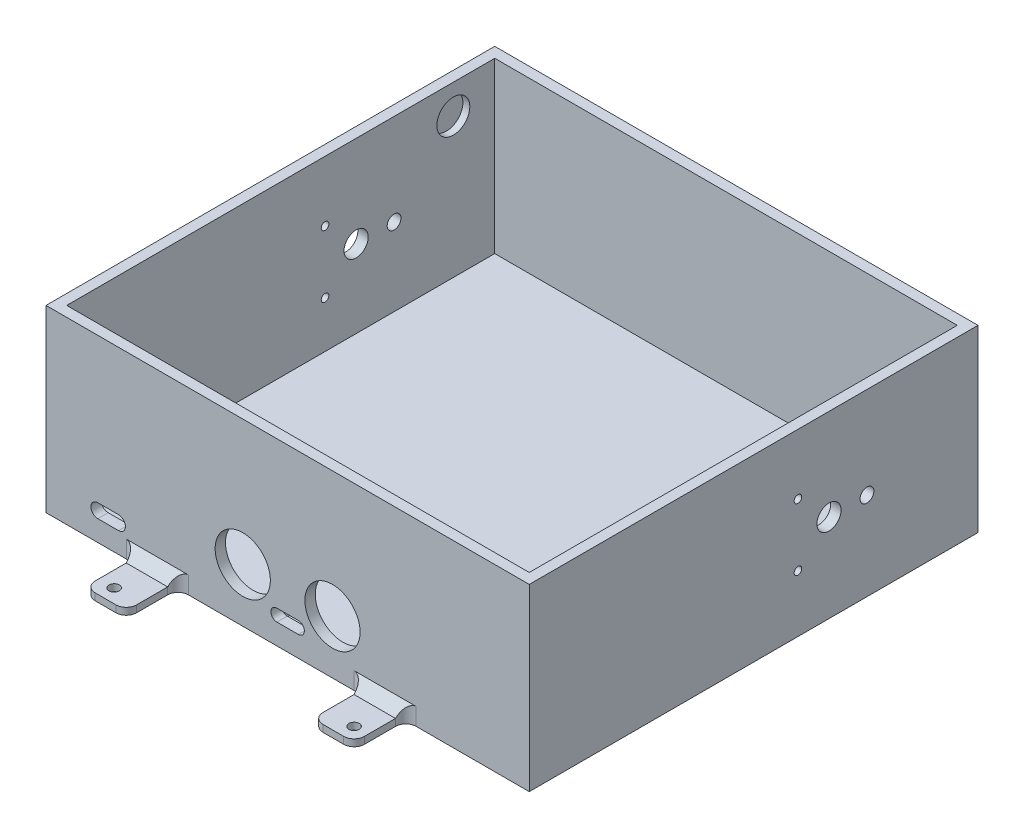
SolidWorks part; units mm, degrees
ref_plane "Front Plane" through (0, 0, 0) normal (0, 0, 1) x (1, 0, 0)
ref_plane "Top Plane" through (0, 0, 0) normal (0, 1, 0) x (1, 0, 0)
ref_plane "Right Plane" through (0, 0, 0) normal (1, 0, 0) x (0, 0, -1)
sketch "Sketch1" plane through (0, 0, 0) normal (0, 1, 0) x (1, 0, 0)
  line L1 (-70, 65) -> (70, 65)
  line L2 (-70, 65) -> (-70, -65)
  line L3 (-70, -65) -> (70, -65)
  line L4 (70, 65) -> (70, -65)
  line L5 (-70, 65) -> (70, -65) construction
  line L6 (-70, -65) -> (70, 65) construction
  point P0 (0, 0)
  dimension "D1" = 130
  dimension "D2" = 140
extrude "Boss-Extrude1" add sketch "Sketch1" along normal blind 52
shell "Shell1" thickness 3 removed face at (0, 52, 0)
sketch "Sketch2" plane through (70, 0, 0) normal (1, 0, 0) x (0, 0, -1)
  line L0 (-65, 0) -> (65, 0) construction
  line L1 (65, 52) -> (65, 0) construction
  circle A0 centre (21.8376, 25.5) radius 3.5
  circle A1 centre (32.8376, 25.5) radius 2
  circle A2 centre (12.8376, 34.5) radius 1.1
  circle A3 centre (12.8376, 16.5) radius 1.1
  dimension "D1" = 7
  dimension "D2" = 4
  dimension "D9" = 2.2
  dimension "D3" = 25.5
  dimension "D4" = 43.1624
  dimension "D5" = 11
  dimension "D6" = 18
  dimension "D7" = 9
  dimension "D8" = 52.1624
extrude "Cut-Extrude1" cut sketch "Sketch2" against normal up to surface (3 mm away) up to face at (67, 27.5, 0)
mirror "Mirror1" about plane through (0, 0, 0) normal (1, 0, 0) of "Cut-Extrude1"
sketch "Sketch3" plane through (0, 3, 0) normal (0, 1, 0) x (1, 0, 0)
  line L0 (-70, -65) -> (70, -65) construction
  line L1 (0, 0) -> (0, -122.9827) construction
  circle A0 centre (-7, -59) radius 1.1
  circle A1 centre (7, -59) radius 1.1
  dimension "D2" = 2.2
  dimension "D1" = 14
  dimension "D3" = 6
extrude "Cut-Extrude2" cut sketch "Sketch3" against normal up to surface (3 mm away) up to face at (0, 0, 0)
sketch "Sketch6" plane through (0, 0, 62) normal (0, 0, -1) x (-1, 0, 0)
  line L4 (55, 8) -> (49, 8) construction
  line L5 (55, 6) -> (49, 6)
  line L6 (55, 10) -> (49, 10)
  line L7 (70, 0) -> (-70, 0) construction
  line L8 (70, 52) -> (70, 0) construction
  arc A0 (55, 6) -> (55, 10) centre (55, 8) ccw
  arc A1 (49, 10) -> (49, 6) centre (49, 8) ccw
  point P2 (52, 8)
  dimension "D2" = 2
  dimension "D1" = 8
  dimension "D3" = 18
  dimension "D4" = 6
extrude "Cut-Extrude4" cut sketch "Sketch6" against normal up to surface (3 mm away) up to face at (0, 26, 65)
sketch "Sketch7" plane through (-67, 0, 0) normal (1, 0, 0) x (0, 0, -1)
  line L0 (62, 52) -> (62, 3) construction
  line L1 (62, 52) -> (-62, 52) construction
  circle A0 centre (50, 43.5) radius 4.775
  dimension "D1" = 9.55
  dimension "D2" = 12
  dimension "D3" = 8.5
extrude "Cut-Extrude5" cut sketch "Sketch7" against normal blind 2
ref_axis "Axis1" through (0, 54.6, 0) along (0, -1, 0)
pattern_circular "CirPattern5" count 2 every 180 about axis through (0, 54.6, 0) along (0, -1, 0) of "Cut-Extrude5"
sketch "Sketch8" plane through (0, 0, 0) normal (0, 1, 0) x (1, 0, 0)
  line L0 (-70, -65) -> (70, -65) construction
  line L1 (-43.75, -65) -> (-31.75, -65)
  line L2 (-43.75, -65) -> (-43.75, -80)
  line L3 (-43.75, -80) -> (-31.75, -80)
  line L4 (34.25, -65) -> (34.25, -80)
  line L5 (-31.75, -80) -> (-31.75, -65)
  line L6 (22.25, -80) -> (22.25, -65)
  line L7 (22.25, -80) -> (34.25, -80)
  line L8 (22.25, -65) -> (34.25, -65)
  line L9 (70, -65) -> (70, 65) construction
  dimension "D1" = 15
  dimension "D2" = 78
  dimension "D3" = 12
  dimension "D4" = 12
  dimension "D5" = 35.75
extrude "Boss-Extrude2" add sketch "Sketch8" along normal blind 2
sketch "Sketch11" plane through (0, 2, 0) normal (0, 1, 0) x (1, 0, 0)
  line L0 (-43.75, -80) -> (-31.75, -80) construction
  line L1 (-43.75, -65) -> (-43.75, -80) construction
  circle A0 centre (-39.25, -76) radius 1.5
  circle A1 centre (30.25, -76) radius 1.5
  dimension "D4" = 3
  dimension "D1" = 69.5
  dimension "D2" = 4
  dimension "D3" = 4.5
extrude "Cut-Extrude7" cut sketch "Sketch11" against normal through all
fillet "Fillet1" radius 3 4 edges at (34.25, 1, 65) (-43.75, 1, 80) (-43.75, 1, 65) (34.25, 1, 80)
fillet "Fillet2" radius 3 4 edges at (22.25, 1, 65) (22.25, 1, 80) (-31.75, 1, 65) (-31.75, 1, 80)
chamfer "Chamfer1" distance 3 angle 45 2 edges at (28.25, 2, 65) (-37.75, 2, 65)
sketch "Sketch12" plane through (0, 0, 65) normal (0, 0, 1) x (1, 0, 0)
  line L0 (-28.75, 0) -> (19.25, 0) construction
  line L1 (0, 0) -> (0, 42.7147) construction
  line L2 (-3.1, 7.75) -> (3.1, 7.75) construction
  line L3 (-3.1, 9.5) -> (3.1, 9.5)
  line L4 (-3.1, 6) -> (3.1, 6)
  circle A0 centre (-13, 15.5) radius 8
  circle A1 centre (13, 15.5) radius 8
  arc A2 (-3.1, 9.5) -> (-3.1, 6) centre (-3.1, 7.75) ccw
  arc A3 (3.1, 6) -> (3.1, 9.5) centre (3.1, 7.75) ccw
  point P11 (0, 7.75)
  dimension "D1" = 16
  dimension "D2" = 26
  dimension "D3" = 15.5
  dimension "D4" = 3.5
  dimension "D5" = 6.2
  dimension "D6" = 7.75
extrude "Cut-Extrude8" cut sketch "Sketch12" against normal blind 10
